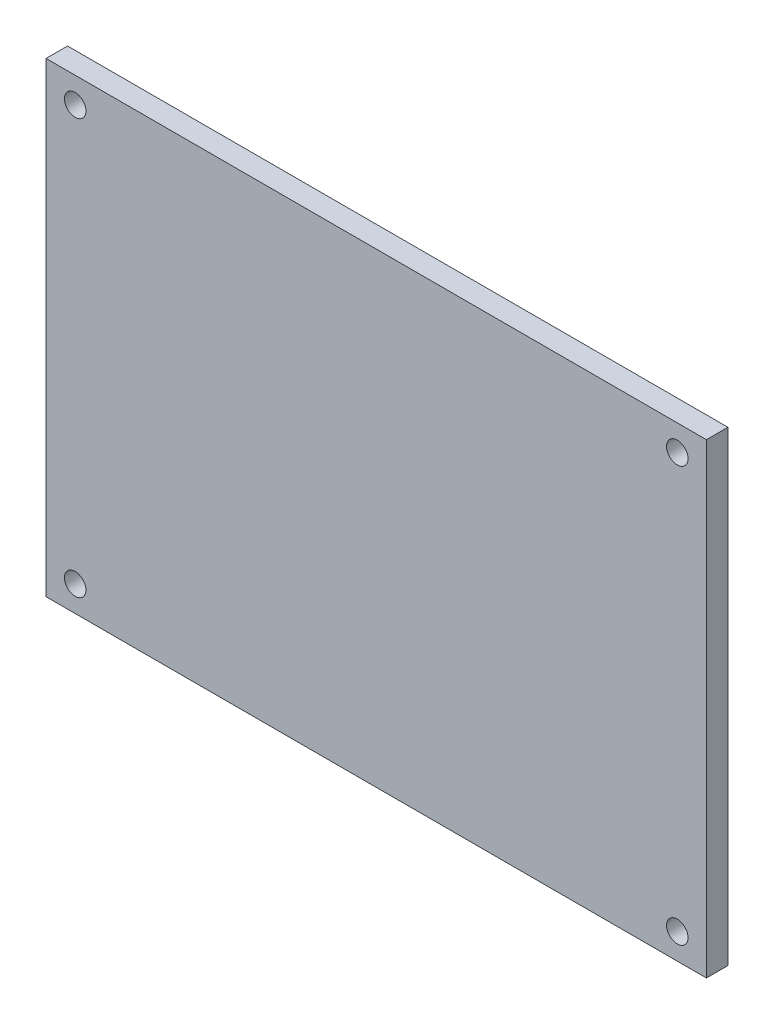
SolidWorks part; units mm, degrees
ref_plane "前视基准面" through (0, 0, 0) normal (0, 0, 1) x (1, 0, 0)
ref_plane "上视基准面" through (0, 0, 0) normal (0, 1, 0) x (1, 0, 0)
ref_plane "右视基准面" through (0, 0, 0) normal (1, 0, 0) x (0, 0, -1)
other "Configuration Table"
sketch "草图1" plane through (0, 0, 0) normal (0, 0, 1) x (1, 0, 0)
  line L1 (-46.0375, -32.5) -> (46.0375, -32.5)
  line L2 (-46.0375, -32.5) -> (-46.0375, 32.5)
  line L3 (-46.0375, 32.5) -> (46.0375, 32.5)
  line L4 (46.0375, -32.5) -> (46.0375, 32.5)
  line L5 (0, 32.5) -> (0, -32.5) construction
  line L6 (-46.0375, 0) -> (46.0375, 0) construction
  line L7 (-41.9735, -28.92) -> (41.9735, -28.92)
  line L8 (-41.9735, -28.92) -> (-41.9735, 28.92)
  line L9 (-41.9735, 28.92) -> (41.9735, 28.92)
  line L10 (41.9735, -28.92) -> (41.9735, 28.92)
  line L11 (-41.9735, -28.92) -> (41.9735, 28.92) construction
  line L12 (-41.9735, 28.92) -> (41.9735, -28.92) construction
  circle A0 centre (-41.9735, 28.92) radius 1.5
  circle A1 centre (41.9735, 28.92) radius 1.5
  circle A2 centre (41.9735, -28.92) radius 1.5
  circle A3 centre (-41.9735, -28.92) radius 1.5
  point P0 (0, 0)
  point P4 (0, 0)
  dimension "D5" = 3
  dimension "D6" = 3
  dimension "D7" = 3
  dimension "D8" = 3
  dimension "D1" = 92.075
  dimension "D2" = 65
  dimension "D3" = 83.947
  dimension "D4" = 57.84
extrude "凸台-拉伸1" add sketch "草图1" along normal blind 3 contours A3 L7 A2 L10 A1 L9 A0 L8 | L1 L4 L3 L2 A3 L8 A0 L9 A1 L10 A2 L7 region at (-44.9104, 0, 0) region at (0, 0, 0)
